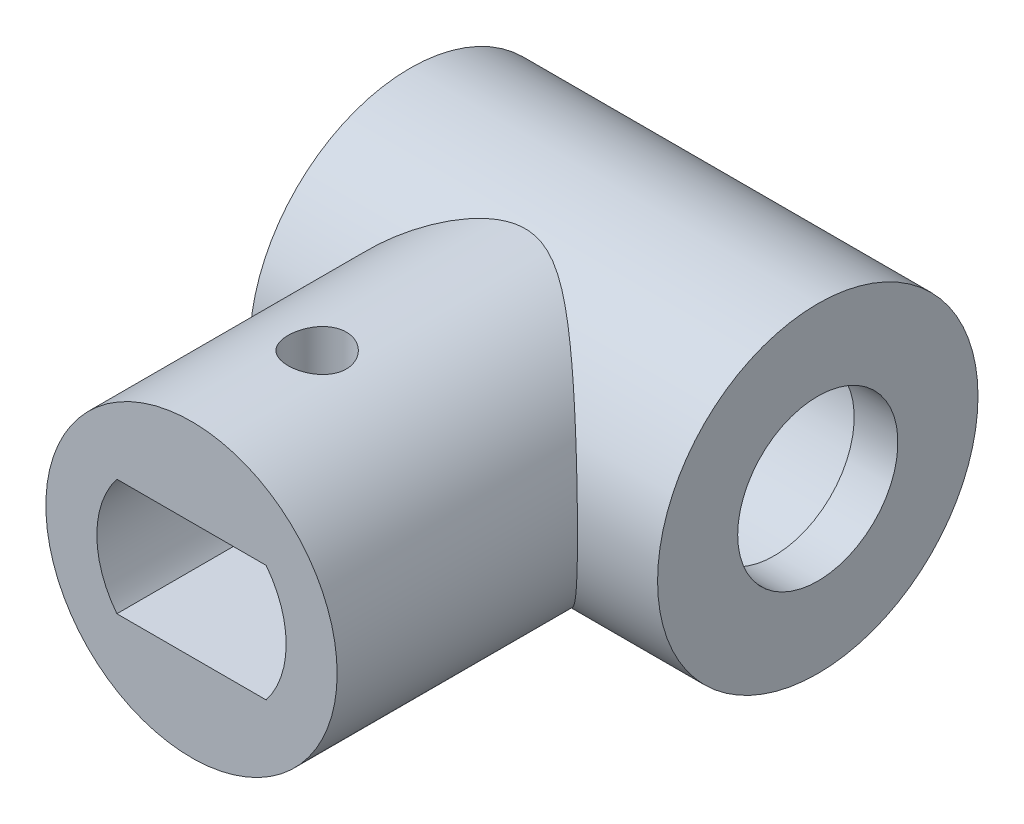
SolidWorks part; units mm, degrees
ref_plane "Front Plane" through (0, 0, 0) normal (0, 0, 1) x (1, 0, 0)
ref_plane "Top Plane" through (0, 0, 0) normal (0, 1, 0) x (1, 0, 0)
ref_plane "Right Plane" through (0, 0, 0) normal (1, 0, 0) x (0, 0, -1)
sketch "Sketch1" plane through (0, 0, 0) normal (0, 0, 1) x (1, 0, 0)
  line L0 (0, 3.2) -> (10, 3.2)
  line L4 (0, 0) -> (10, 0) construction
  line L5 (10, 3.2) -> (10, 2.2)
  line L6 (10, 2.2) -> (10, 0) construction
  line L7 (0, 3.2) -> (0, 0) construction
  dimension "D1" = 10
  dimension "D2" = 1
  dimension "D3" = 6.4
revolve "Revolve-Thin1" add sketch "Sketch1" angle 360 about L4 wall 1.2
ref_plane "Plane1" through (0, 0, 11) normal (0, 0, 1) x (1, 0, 0)
sketch "Sketch2" plane through (0, 0, 11) normal (0, 0, 1) x (1, 0, 0)
  line L0 (0, 0) -> (5, 0) construction
  line L1 (3, 1.5) -> (7, 1.5)
  line L2 (3, -1.5) -> (7, -1.5)
  arc A0 (3, 1.5) -> (3, -1.5) centre (5, 0) ccw
  arc A1 (7, 1.5) -> (3, 1.5) centre (5, 0) ccw construction
  arc A2 (7, -1.5) -> (7, 1.5) centre (5, 0) ccw
  arc A3 (3, -1.5) -> (7, -1.5) centre (5, 0) ccw construction
  circle A4 centre (5, 0) radius 4
  dimension "D1" = 5
  dimension "D4" = 1.5
  dimension "D2" = 3
  dimension "D3" = 5
extrude "Boss-Extrude1" add sketch "Sketch2" against normal up to surface (6.6 mm away) up to face at (11.2, 0, 4.4)
other "Move Face1" flip direction yes face at (2.75, -0.003, 7.6341) face at (5, 1.5, 7.5682) face at (7.25, 0.003, 7.6341) face at (5, -1.5, 7.5682) offset 0.1 parameters "D1"=0.1
sketch "Sketch3" plane through (0, -1.6, 0) normal (0, 1, 0) x (1, 0, 0)
  line L0 (2.9506, -7.5494) -> (7.0494, -7.5494) construction
  line L1 (2.9506, -4.0988) -> (2.9506, -11) construction
  line L4 (7.0494, -11) -> (7.0494, -4.0988)
  line L5 (7.0494, -4.0988) -> (2.9506, -4.0988)
  line L6 (2.9506, -4.0988) -> (2.9506, -11)
  line L7 (2.9506, -11) -> (7.0494, -11)
  line L8 (7.0494, -11) -> (7.0494, -4.0988) construction
  line L9 (7.0494, -4.0988) -> (2.9506, -4.0988) construction
  line L10 (2.9506, -4.0988) -> (2.9506, -11) construction
  line L11 (2.9506, -11) -> (7.0494, -11) construction
  circle A0 centre (5, -7.5494) radius 0.8
  point P8 (5, -7.5494)
  dimension "D1" = 1.6
  dimension "D2" = 0
extrude "Cut-Extrude1" cut sketch "Sketch3" against normal through all both and the other way through all
